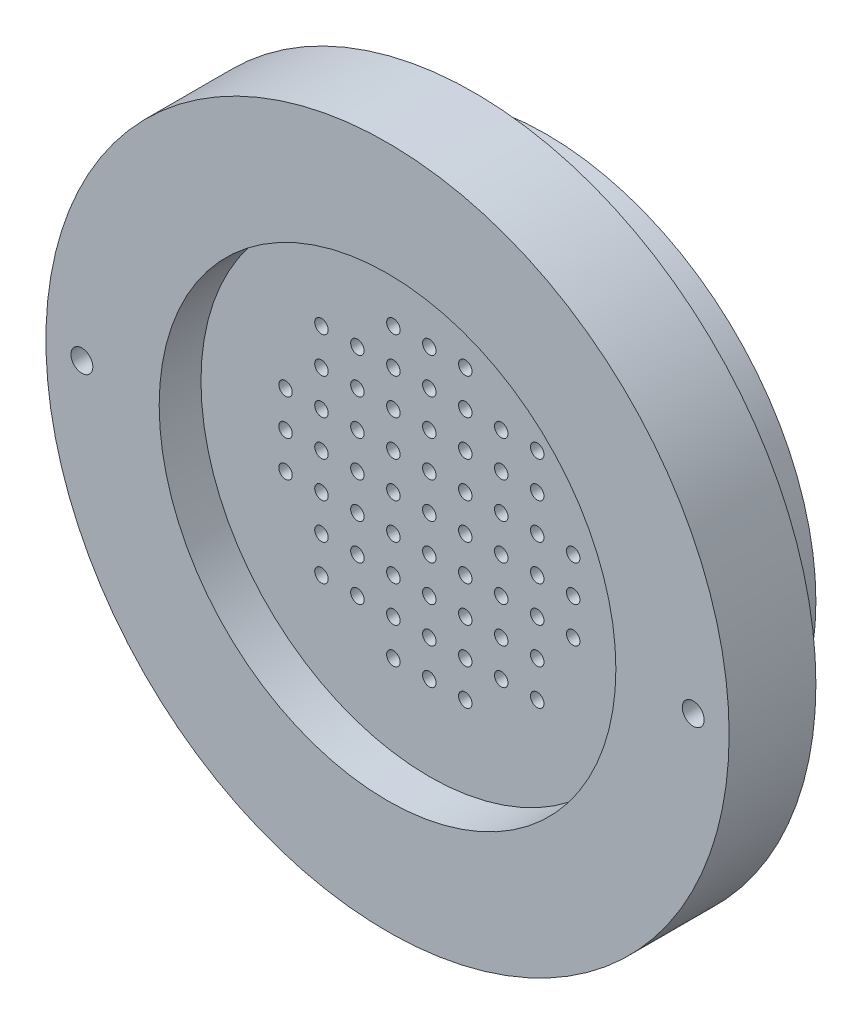
SolidWorks part; units mm, degrees
ref_plane "Plan de face" through (0, 0, 0) normal (0, 0, 1) x (1, 0, 0)
ref_plane "Plan de dessus" through (0, 0, 0) normal (0, 1, 0) x (1, 0, 0)
ref_plane "Plan de droite" through (0, 0, 0) normal (1, 0, 0) x (0, 0, -1)
sketch "Sketch1" plane through (0, 0, 0) normal (0, 0, 1) x (1, 0, 0)
  circle A0 centre (0, 0) radius 38
extrude "Boss-Extrude1" add sketch "Sketch1" along normal blind 5
sketch "Sketch2" plane through (0, 0, 5) normal (0, 0, 1) x (1, 0, 0)
  circle A0 centre (0, 0) radius 0.75
extrude "Cut-Extrude1" cut sketch "Sketch2" against normal through all
pattern_linear "LPattern1" count 5 spacing 4 along (0, 1, 0) count 5 spacing 4 along (1, 0, 0) skipping (2, 4), (3, 4), (4, 2), (4, 3), (4, 4) of "Cut-Extrude1"
mirror "Mirror1" about plane through (0, 0, 0) normal (1, 0, 0) of "LPattern1" second plane through (0, 0, 0) second plane normal (0, 1, 0)
sketch "Sketch16" plane through (0, 0, 5) normal (0, 0, 1) x (1, 0, 0)
  circle A0 centre (0, 0) radius 25.4
  circle A1 centre (0, 0) radius 38
extrude "Boss-Extrude2" add sketch "Sketch16" along normal blind 4.65
sketch "Sketch17" plane through (0, 0, 0) normal (0, 0, -1) x (-1, 0, 0)
  circle A0 centre (0, 0) radius 25.4
  circle A1 centre (0, 0) radius 30
extrude "Boss-Extrude3" add sketch "Sketch17" along normal blind 8
sketch "Sketch20" plane through (0, 0, 0) normal (0, 0, -1) x (-1, 0, 0)
  line L0 (-30, 0) -> (-38, 0)
  circle A0 centre (0, 0) radius 30 construction
  circle A1 centre (0, 0) radius 38 construction
hole_wizard "CBORE for #2 Binding Head Machine Screw1" positions "Sketch24" profile "Sketch25" counterbore size "#2" standard "ANSI Inch" end condition through all
sketch "Sketch24" plane through (0, 0, 0) normal (0, 0, -1) x (-1, 0, 0)
  line L0 (-30, 0) -> (-38, 0) construction
  point P0 (-34, 0)
sketch "Sketch25" plane through (34, 0, 0) normal (1, 0, 0) x (0, 1, 0)
  line L0 (0, 0) -> (0, 9.65)
  line L1 (0, 9.65) -> (1.2192, 9.65)
  line L3 (1.2192, 9.65) -> (1.2192, 1.27)
  line L4 (1.2192, 1.27) -> (2.7788, 1.27)
  line L5 (2.7788, 1.27) -> (2.7788, 0)
  line L7 (2.7788, 0) -> (0, 0)
  line L11 (0, -6.35) -> (0, 107.95) construction
  dimension "Thru Hole Dia." = 2.4384
  dimension "Thru Hole Depth" = 9.65
  dimension "C'Bore Dia." = 5.5575
  dimension "C'Bore Depth" = 1.27
mirror "Mirror2" about plane through (0, 0, 0) normal (1, 0, 0) of "CBORE for #2 Binding Head Machine Screw1"
